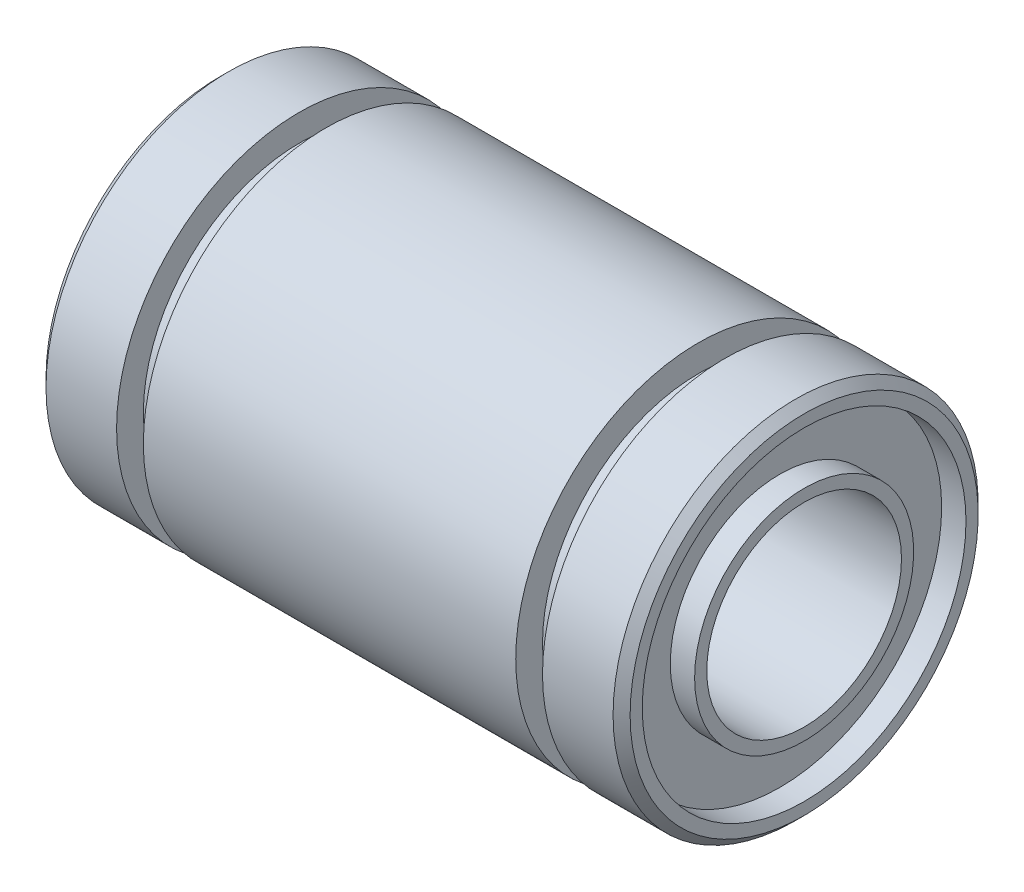
SolidWorks part; units mm, degrees
material "1060 Alloy"
ref_plane "Front Plane" through (0, 0, 0) normal (0, 0, 1) x (1, 0, 0)
ref_plane "Top Plane" through (0, 0, 0) normal (0, 1, 0) x (1, 0, 0)
ref_plane "Right Plane" through (0, 0, 0) normal (1, 0, 0) x (0, 0, -1)
sketch "Sketch1" plane through (0, 0, 0) normal (0, 0, 1) x (1, 0, 0)
  line L0 (-45.6895, 0) -> (45.6895, 0) construction
  line L1 (-11.65, 7.5) -> (-8.75, 7.5)
  line L2 (-8.75, 7.5) -> (-8.75, 6.4)
  line L3 (-8.75, 6.4) -> (-7.65, 6.4)
  line L4 (-7.65, 6.4) -> (-7.65, 7.5)
  line L5 (-7.65, 7.5) -> (7.65, 7.5)
  line L6 (0, 45.6895) -> (0, -45.6895) construction
  line L7 (-11.65, 7.5) -> (-12, 7.15)
  line L8 (-12, 7.15) -> (-12, 6.65)
  line L9 (-12, 6.65) -> (-11, 6.65)
  line L10 (-11, 6.65) -> (-11, 4.5)
  line L11 (-11, 4.5) -> (-12, 4.5)
  line L12 (-12, 4.5) -> (-12, 4)
  line L13 (-12, 4) -> (12, 4)
  line L14 (12, 4.5) -> (12, 4)
  line L15 (11, 4.5) -> (12, 4.5)
  line L16 (11, 6.65) -> (11, 4.5)
  line L17 (12, 6.65) -> (11, 6.65)
  line L18 (12, 7.15) -> (12, 6.65)
  line L19 (11.65, 7.5) -> (12, 7.15)
  line L20 (7.65, 6.4) -> (7.65, 7.5)
  line L21 (8.75, 6.4) -> (7.65, 6.4)
  line L22 (8.75, 7.5) -> (8.75, 6.4)
  line L23 (11.65, 7.5) -> (8.75, 7.5)
  point P19 (0, 4)
  point P26 (0, 7.5)
  dimension "D1" = 45
  dimension "D2" = 1.1
  dimension "L" = 24
  dimension "B" = 17.5
  dimension "W" = 1.1
  dimension "D" = 7.5
  dimension "D_1" = 7.15
  dimension "D3" = 0.5
  dimension "dr" = 4
  dimension "D4" = 0.5
  dimension "D5" = 1
revolve "Revolve1" add sketch "Sketch1" angle 360 about L0 region at (0, 5.7195, 0)
equation "\"D\"=15"
equation "\"D1\"=14.3"
equation "\"dr\"=8"
equation "\"L\"=24"
equation "\"B\"=17.5"
equation "\"W\"=1.1"
equation "\"L@Sketch1\"= \"L\""
equation "\"B@Sketch1\"= \"B\""
equation "\"W@Sketch1\"= \"W\""
equation "\"dr@Sketch1\"= \"dr\" * 0.5"
equation "\"D@Sketch1\" = \"D\" * 0.5"
equation "\"D_1@Sketch1\" = \"D1\" * 0.5"
